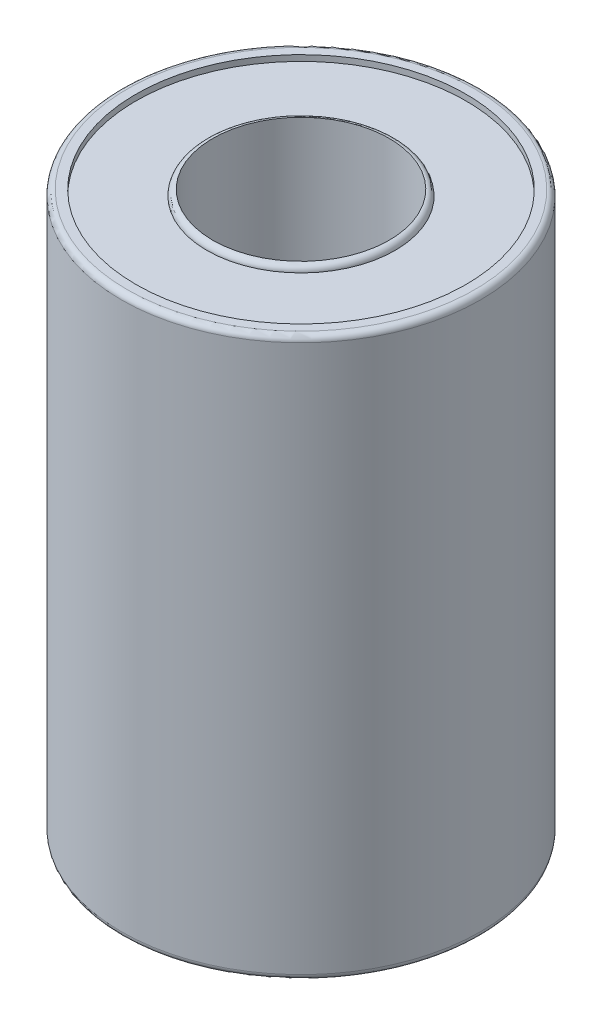
SolidWorks part; units mm, degrees
ref_plane "Front" through (0, 0, 0) normal (0, 0, 1) x (1, 0, 0)
ref_plane "Top" through (0, 0, 0) normal (0, 1, 0) x (1, 0, 0)
ref_plane "Right" through (0, 0, 0) normal (1, 0, 0) x (0, 0, -1)
sketch "草图1" plane through (0, 0, 0) normal (0, 1, 0) x (1, 0, 0)
  circle A0 centre (0, 0) radius 6
  circle A1 centre (0, 0) radius 3
  dimension "D1" = 12
  dimension "D2" = 6
extrude "凸台-拉伸1" add sketch "草图1" along normal blind 18.6 from offset 0.2
sketch "草图2" plane through (0, 0, 0) normal (0, 1, 0) x (1, 0, 0)
  circle A0 centre (0, 0) radius 3
  circle A1 centre (0, 0) radius 3.2
  circle A2 centre (0, 0) radius 6.1084
  circle A3 centre (0, 0) radius 5.6084
  dimension "D1" = 0.2
  dimension "D2" = 0.5
extrude "凸台-拉伸2" add sketch "草图2" along normal blind 19 contours A2 A3 | A1 A0 region at (-3.1095, 0, 0) region at (-5.9356, 0, 0)
fillet "圆角1" radius 0.2 4 edges at (0, 19, 3.2) (0, 0, 3.2) (0, 0, 6.1084) (0, 19, 6.1084)
